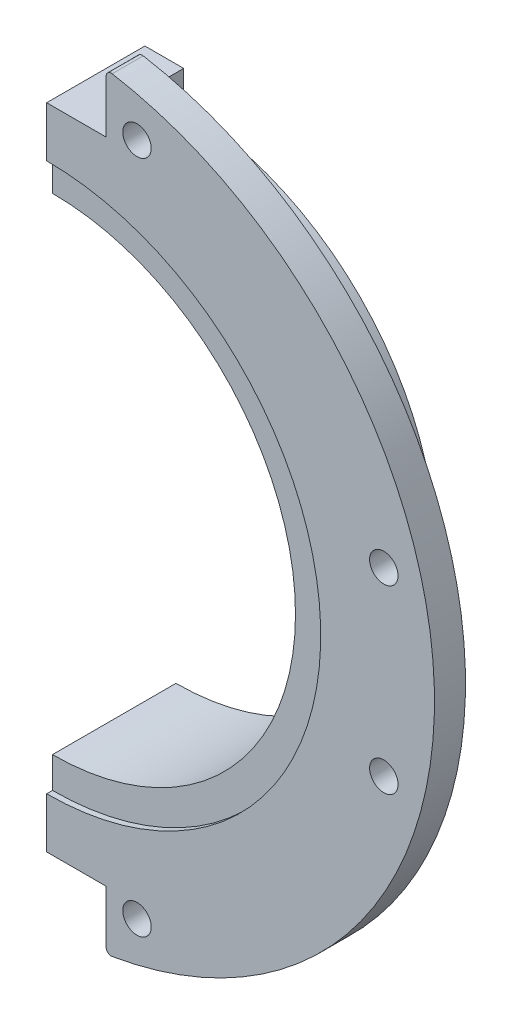
SolidWorks part; units mm, degrees
ref_plane "Front" through (0, 0, 0) normal (0, 0, 1) x (1, 0, 0)
ref_plane "Top" through (0, 0, 0) normal (0, 1, 0) x (1, 0, 0)
ref_plane "Right" through (0, 0, 0) normal (1, 0, 0) x (0, 0, -1)
sketch "Sketch1" plane through (0, 0, 0) normal (0, 0, 1) x (1, 0, 0)
  line L1 (0, 0) -> (180, 0)
  line L2 (0, 0) -> (0, 180)
  line L3 (0, 180) -> (180, 180)
  line L4 (180, 0) -> (180, 180)
  dimension "D1" = 180
extrude "Boss-Extrude1" add sketch "Sketch1" along normal blind 6
sketch "Sketch2" plane through (0, 0, 0) normal (0, 0, -1) x (-1, 0, 0)
  line L0 (0, 90) -> (-180, 90) construction
  line L1 (0, 180) -> (0, 0) construction
  line L3 (-180, 0) -> (-180, 180) construction
  circle A0 centre (-90, 90) radius 46.3
  circle A1 centre (-90, 90) radius 50.3
  point P11 (-90, 90)
  dimension "D1" = 92.6
  dimension "D2" = 4
extrude "Boss-Extrude2" add sketch "Sketch2" along normal blind 19
sketch "Sketch3" plane through (0, 0, 0) normal (0, 0, -1) x (-1, 0, 0)
  circle A0 centre (-90, 90) radius 47
  dimension "D1" = 94
extrude "Cut-Extrude1" cut sketch "Sketch3" against normal through all both and the other way through all
sketch "Sketch4" plane through (0, 0, 0) normal (0, 0, -1) x (-1, 0, 0)
  line L0 (0, 77.5) -> (0, 102.5)
  line L1 (0, 180) -> (0, 0) construction
  line L2 (0, 77.5) -> (-41.2779, 77.5)
  line L3 (0, 102.5) -> (-41.2779, 102.5)
  circle A0 centre (-90, 90) radius 50.3 construction
  arc A1 (-41.2779, 77.5) -> (-41.2779, 102.5) centre (-90, 90) ccw
  point P2 (0, 90)
  point P5 (0, 90)
  dimension "D1" = 25
extrude "Boss-Extrude3" add sketch "Sketch4" along normal blind 60
ref_plane "Plane1" through (0, 90, 0) normal (0, -1, 0) x (-1, 0, 0)
fillet "Fillet4" radius 3 2 edges at (41.2779, 77.5, -9.5) (41.2779, 102.5, -9.5)
hole_wizard "M5 Clearance Hole1" positions "Sketch11" profile "Sketch12" hole size "M5" standard "ANSI Metric" end condition up to next
sketch "Sketch11" plane through (0, 0, 0) normal (0, 0, -1) x (-1, 0, 0)
  point P52 (-107.4703, 155.2)
  point P58 (-155.2, 107.4703)
  point P61 (-155.2, 72.5297)
  point P67 (-107.4703, 24.8)
  point P70 (-72.5297, 24.8)
  point P76 (-24.8, 72.5297)
  point P79 (-24.8, 107.4703)
  point P85 (-72.5297, 155.2)
sketch "Sketch12" plane through (107.4703, 155.2, 0) normal (1, 0, 0) x (0, 1, 0)
  line L0 (0, 0) -> (0, 6)
  line L1 (0, 6) -> (2.75, 6)
  line L2 (2.75, 6) -> (2.75, 0)
  line L5 (2.75, 0) -> (0, 0)
  line L11 (0, -6.35) -> (0, 107.95) construction
  dimension "Thru Hole Dia." = 5.5
  dimension "Thru Hole Depth" = 6
sketch "Sketch15" plane through (0, 0, 0) normal (0, 0, -1) x (-1, 0, 0)
  line L0 (-180, 90) -> (-90, 90) construction
  line L3 (-180, 0) -> (-180, 180) construction
  line L4 (-137.3, 93.5) -> (-137.3, 86.5)
  line L5 (-137.3, 93.5) -> (-162.3, 93.5)
  line L6 (-162.3, 93.5) -> (-162.3, 86.5)
  line L7 (-137.3, 86.5) -> (-162.3, 86.5)
  line L8 (-93.5, 42.7) -> (-86.5, 36.7) construction
  line L9 (-93.5, 36.7) -> (-86.5, 42.7) construction
  arc A0 (-41.8739, 104.6276) -> (-41.8739, 75.3724) centre (-90, 90) ccw construction
  point P4 (-137.3, 90)
  point P6 (-90, 39.7)
  dimension "D1" = 7
  dimension "D2" = 25
  dimension "D3" = 47.3
sketch "Sketch30" plane through (0, 90, 0) normal (0, -1, 0) x (-1, 0, 0)
  line L1 (22.1625, 78.3225) -> (-206.3555, 78.3225)
  line L2 (22.1625, 78.3225) -> (22.1625, -34.6262)
  line L3 (22.1625, -34.6262) -> (-206.3555, -34.6262)
  line L4 (-206.3555, 78.3225) -> (-206.3555, -34.6262)
sketch "Sketch31" plane through (0, 0, 6) normal (0, 0, 1) x (1, 0, 0)
  line L2 (0, 180) -> (0, 0) construction
  line L3 (0, 0) -> (180, 0) construction
  line L4 (180, 0) -> (180, 180) construction
  line L5 (180, 180) -> (0, 180) construction
  line L8 (0, 180) -> (0, 102.5)
  line L9 (0, 0) -> (180, 0)
  line L10 (180, 0) -> (180, 180)
  line L11 (180, 180) -> (0, 180)
  line L12 (0, 77.5) -> (0, 0)
  line L13 (41.2779, 77.5) -> (0, 77.5) construction
  line L14 (0, 102.5) -> (41.2779, 102.5) construction
  line L15 (16.049, 77.5) -> (0, 77.5)
  line L16 (0, 102.5) -> (16.049, 102.5)
  circle A4 centre (90, 90) radius 75 construction
  arc A5 (16.049, 77.5) -> (16.049, 102.5) centre (90, 90) ccw
extrude "Cut-Extrude4" cut sketch "Sketch31" against normal up to next contours A5 L16 L8 L11 L10 L9 L12 L15
sketch "Sketch33" plane through (0, 0, 6) normal (0, 0, 1) x (1, 0, 0)
  line L1 (0, 102.5) -> (1, 102.5)
  line L2 (0, 102.5) -> (0, 77.5)
  line L3 (0, 77.5) -> (1, 77.5)
  line L4 (1, 102.5) -> (1, 77.5)
  dimension "D1" = 1
extrude "Cut-Extrude5" cut sketch "Sketch33" against normal up to next
sketch "Sketch35" plane through (0, 0, 0) normal (0, 0, -1) x (-1, 0, 0)
  line L0 (-90, 15) -> (-90, 165) construction
  line L4 (-97.5, 152.7377) -> (-82.5, 152.7377)
  line L5 (-97.5, 152.7377) -> (-97.5, 139.7377)
  line L6 (-97.5, 139.7377) -> (-82.5, 139.7377)
  line L7 (-82.5, 152.7377) -> (-82.5, 139.7377)
  line L8 (-97.5, 40.2623) -> (-82.5, 40.2623)
  line L9 (-97.5, 40.2623) -> (-97.5, 27.2623)
  line L10 (-97.5, 27.2623) -> (-82.5, 27.2623)
  line L11 (-82.5, 40.2623) -> (-82.5, 27.2623)
  arc A0 (-16.049, 102.5) -> (-16.049, 77.5) centre (-90, 90) ccw construction
  arc A1 (-41.8739, 104.6276) -> (-41.8739, 75.3724) centre (-90, 90) ccw construction
  arc A2 (-41.8739, 104.6276) -> (-41.8739, 75.3724) centre (-90, 90) ccw construction
  point P8 (-90, 90)
  point P18 (-90, 152.7377)
  point P26 (-90, 27.2623)
  dimension "D1" = 15
  dimension "D2" = 13
  dimension "D3" = 13
  dimension "D4" = 15
extrude "Boss-Extrude6" add sketch "Sketch35" along normal blind 13
hole_wizard "M5 Clearance Hole2" positions "Sketch38" profile "Sketch39" hole size "M5" standard "ANSI Metric" end condition through all
sketch "Sketch38" plane through (97.5, 0, 0) normal (1, 0, 0) x (0, 0, -1)
  line L0 (13, 152.7377) -> (0, 152.7377) construction
  line L1 (13, 40.2623) -> (13, 27.2623) construction
  line L2 (13, 152.7377) -> (13, 139.7377) construction
  point P0 (6.5, 146.2377)
  point P3 (6.5, 33.7623)
  point P8 (6.5, 152.7377)
  point P12 (13, 33.7623)
  point P15 (13, 146.2377)
sketch "Sketch39" plane through (97.5, 146.2377, -6.5) normal (0, 1, 0) x (0, 0, -1)
  line L0 (0, 0) -> (0, 96.5)
  line L1 (0, 96.5) -> (2.75, 96.5)
  line L2 (2.75, 96.5) -> (2.75, 0)
  line L5 (2.75, 0) -> (0, 0)
  line L11 (0, -6.35) -> (0, 107.95) construction
  dimension "Thru Hole Dia." = 5.5
  dimension "Thru Hole Depth" = 96.5
sketch "Sketch40" plane through (82.5, 0, 0) normal (-1, 0, 0) x (0, 0, 1)
  line L0 (-13, 139.7377) -> (-13, 152.7377) construction
  line L1 (-10.75, 143.784) -> (-6.5, 141.3302)
  line L2 (-6.5, 141.3302) -> (-2.25, 143.784)
  line L3 (-2.25, 143.784) -> (-2.25, 148.6915)
  line L4 (-2.25, 148.6915) -> (-6.5, 151.1452)
  line L5 (-6.5, 151.1452) -> (-10.75, 148.6915)
  line L6 (-10.75, 148.6915) -> (-10.75, 143.784)
  line L7 (-13, 27.2623) -> (-13, 139.7377) construction
  line L8 (-2.25, 31.3085) -> (-2.25, 36.216)
  line L9 (-2.25, 36.216) -> (-6.5, 38.6698)
  line L10 (-6.5, 38.6698) -> (-10.75, 36.216)
  line L11 (-10.75, 36.216) -> (-10.75, 31.3085)
  line L12 (-10.75, 31.3085) -> (-6.5, 28.8548)
  line L13 (-6.5, 28.8548) -> (-2.25, 31.3085)
  circle A0 centre (-6.5, 146.2377) radius 4.25 construction
  circle A1 centre (-6.5, 33.7623) radius 4.25 construction
  dimension "D1" = 8.5
  dimension "D2" = 8.5
extrude "Cut-Extrude6" cut sketch "Sketch40" against normal blind 4.2
sketch "Sketch41" plane through (0, 0, 0) normal (0, 0, -1) x (-1, 0, 0)
  line L0 (-90, 15) -> (-90, 165) construction
  line L2 (22.1625, 90) -> (-206.3555, 90) construction
  line L3 (-101.5, 152.7377) -> (-78.5, 152.7377)
  line L4 (-101.5, 152.7377) -> (-101.5, 167.7377)
  line L5 (-101.5, 167.7377) -> (-78.5, 167.7377)
  line L6 (-78.5, 152.7377) -> (-78.5, 167.7377)
  line L7 (-14.4828, 90) -> (-165.5172, 90) construction
  line L8 (-78.5, 27.2623) -> (-78.5, 12.2623)
  line L9 (-101.5, 12.2623) -> (-78.5, 12.2623)
  line L10 (-101.5, 27.2623) -> (-101.5, 12.2623)
  line L11 (-101.5, 27.2623) -> (-78.5, 27.2623)
  line L14 (-82.5, 152.7377) -> (-97.5, 152.7377) construction
  arc A0 (-16.049, 102.5) -> (-16.049, 77.5) centre (-90, 90) ccw construction
  point P7 (-90, 90)
  point P15 (-90, 152.7377)
  point P24 (-90, 90)
  dimension "D1" = 15
  dimension "D2" = 23
extrude "Cut-Extrude7" cut sketch "Sketch41" against normal up to next
fillet "Fillet8" radius 1 4 edges at (101.5, 164.1131, 3) (78.5, 164.1131, 3) (101.5, 15.8869, 3) (78.5, 15.8869, 3)
sketch "Sketch42" plane through (0, 102.5, 0) normal (0, 1, 0) x (1, 0, 0)
  line L0 (15, -6) -> (1, 24)
  line L1 (165, -6) -> (15, -6) construction
  line L2 (1, -6) -> (16.049, -6) construction
  line L3 (1, 60) -> (1, -6) construction
  line L4 (1, 24) -> (1, -6)
  line L5 (1, -6) -> (15, -6)
  dimension "D1" = 30
  dimension "D2" = 14
extrude "Cut-Extrude8" cut sketch "Sketch42" against normal up to next
ref_plane "Plane3" through (90, 0, 0) normal (1, 0, 0) x (0, 0, -1)
sketch "Sketch43" plane through (90, 0, 0) normal (1, 0, 0) x (0, 0, -1)
  line L1 (-26.2287, 173.6103) -> (66.8607, 173.6103)
  line L2 (-26.2287, 173.6103) -> (-26.2287, 11.2507)
  line L3 (-26.2287, 11.2507) -> (66.8607, 11.2507)
  line L4 (66.8607, 173.6103) -> (66.8607, 11.2507)
sketch "Sketch46" plane through (0, 0, 0) normal (0, 0, -1) x (-1, 0, 0)
  line L0 (-101.5, 162.9366) -> (-101.5, 172.9366)
  line L1 (-101.5, 172.9366) -> (-111.5, 172.9366)
  line L2 (-111.5, 172.9366) -> (-111.5, 161.8523)
  line L9 (-101.5, 152.7377) -> (-101.5, 162.9366)
  line L10 (-101.5, 17.0634) -> (-101.5, 27.2623)
  line L11 (-101.5, 27.2623) -> (-97.5, 27.2623)
  line L12 (-97.5, 27.2623) -> (-97.5, 40.2623)
  line L16 (-97.5, 139.7377) -> (-97.5, 152.7377)
  line L17 (-97.5, 152.7377) -> (-101.5, 152.7377)
  line L18 (-101.5, 152.7377) -> (-101.5, 162.9366)
  line L19 (-101.5, 17.0634) -> (-101.5, 27.2623)
  line L20 (-101.5, 27.2623) -> (-97.5, 27.2623)
  line L21 (-97.5, 27.2623) -> (-97.5, 40.2623)
  line L25 (-97.5, 139.7377) -> (-97.5, 152.7377)
  line L26 (-97.5, 152.7377) -> (-101.5, 152.7377)
  arc A5 (-101.5, 162.9366) -> (-102.6689, 163.9222) centre (-102.5, 162.9366) ccw
  arc A6 (-102.6689, 163.9222) -> (-102.6689, 16.0778) centre (-90, 90) ccw
  arc A7 (-102.6689, 16.0778) -> (-101.5, 17.0634) centre (-102.5, 17.0634) ccw
  arc A8 (-97.5, 139.7377) -> (-97.5, 40.2623) centre (-90, 90) ccw
  arc A10 (-101.5, 162.9366) -> (-102.6689, 163.9222) centre (-102.5, 162.9366) ccw
  arc A11 (-102.6689, 163.9222) -> (-102.6689, 16.0778) centre (-90, 90) ccw
  arc A12 (-102.6689, 16.0778) -> (-101.5, 17.0634) centre (-102.5, 17.0634) ccw
  arc A13 (-97.5, 139.7377) -> (-97.5, 40.2623) centre (-90, 90) ccw
  arc M18 (-101.5, 162.9366) -> (-102.6689, 163.9222) centre (-102.5, 162.9366) ccw
  arc M19 (-102.6689, 163.9222) -> (-102.6689, 16.0778) centre (-90, 90) ccw
  dimension "D2" = 10
  dimension "D3" = 10
  dimension "D1" = 0
extrude "Boss-Extrude8" [suppressed] add sketch "Sketch46" against normal up to surface (6 mm away) contours L1 L2 L0 M19 M18 up to face at (74.0539, 90, 6)
ref_plane "Plane5" [suppressed] through (90, 0, 0) normal (1, 0, 0) x (0, 0, -1)
mirror "Mirror2" [suppressed] about plane through (90, 0, 0) normal (1, 0, 0)
ref_plane "Plane4" [suppressed] through (0, 90, 0) normal (0, 1, 0) x (1, 0, 0)
mirror "Mirror1" [suppressed] about plane through (0, 90, 0) normal (0, 1, 0)
fillet "Fillet10" [suppressed] radius 1
sketch "Sketch47" plane through (0, 0, 6) normal (0, 0, 1) x (1, 0, 0)
  circle A0 centre (90, 90) radius 53
  circle A1 centre (90, 90) radius 47 construction
  dimension "D1" = 106
extrude "Cut-Extrude10" cut sketch "Sketch47" against normal blind 1.12
ref_plane "Plane6" through (0, 0, -5) normal (0, 0, 1) x (1, 0, 0)
sketch "Sketch51" plane through (0, 0, -13) normal (0, 0, -1) x (-1, 0, 0)
  line L0 (-82.5, 152.7377) -> (-97.5, 152.7377) construction
  line L1 (60, 190) -> (-90, 190)
  line L2 (60, 190) -> (60, -10)
  line L3 (60, -10) -> (-90, -10)
  line L4 (-90, 190) -> (-90, -10)
  point P6 (-90, 152.7377)
  dimension "D1" = 150
  dimension "D2" = 200
extrude "Cut-Extrude12" cut sketch "Sketch51" against normal through all both and the other way through all
